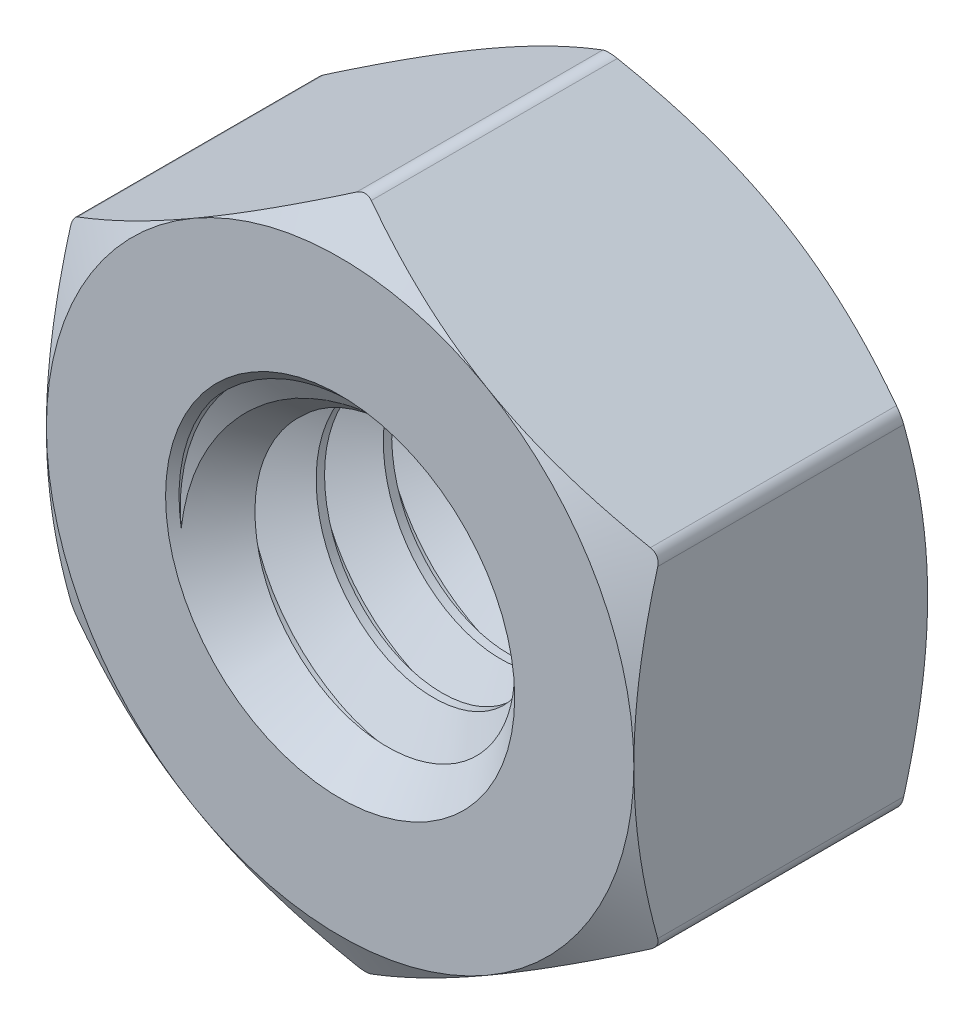
SolidWorks part; units mm, degrees
ref_plane "Front" through (0, 0, 0) normal (0, 0, 1) x (1, 0, 0)
ref_plane "Top" through (0, 0, 0) normal (0, 1, 0) x (1, 0, 0)
ref_plane "Right" through (0, 0, 0) normal (1, 0, 0) x (0, 0, -1)
sketch "Sketch1" plane through (0, 0, 0) normal (0, 0, 1) x (1, 0, 0)
  line L0 (0, 3.175) -> (0, 1.905) construction
  line L1 (-5.5563, 3.2079) -> (-5.5562, -3.2079)
  line L2 (-5.5562, -3.2079) -> (0, -6.4158)
  line L3 (0, -6.4158) -> (5.5562, -3.2079)
  line L4 (5.5562, -3.2079) -> (5.5562, 3.2079)
  line L5 (5.5562, 3.2079) -> (0, 6.4158)
  line L6 (0, 6.4158) -> (-5.5563, 3.2079)
  circle A0 centre (0, 0) radius 5.5562 construction
  circle A1 centre (0, 0) radius 3.175 construction
  point P10 (0, 3.175)
  dimension "Width" = 11.1125
  dimension "Thread Size" = 6.35
  dimension "Thread Pitch" = 1.27
sketch "Sketch2" plane through (0, 0, 0) normal (1, 0, 0) x (0, 0, -1)
  line L0 (-2.7781, 0) -> (2.7781, 0) construction
  line L1 (-2.7781, 6.4158) -> (2.7781, 6.4158) construction
  dimension "Height" = 5.5562
sketch "Sketch15" plane through (0, 0, 0) normal (0, 0, 1) x (1, 0, 0)
  line L1 (0, 6.4158) -> (-5.5563, 3.2079)
  line L2 (-5.5563, 3.2079) -> (-5.5563, -3.2079)
  line L3 (-5.5563, -3.2079) -> (0, -6.4158)
  line L4 (0, -6.4158) -> (5.5563, -3.2079)
  line L5 (5.5563, -3.2079) -> (5.5563, 3.2079)
  line L6 (5.5563, 3.2079) -> (0, 6.4158)
  circle A0 centre (0, 0) radius 5.5563 construction
extrude "Boss-Extrude2" add sketch "Sketch15" along normal mid plane 5.5562
sketch "Sketch16" plane through (0, 0, 0) normal (0, 0, 1) x (1, 0, 0)
  circle A0 centre (0, 0) radius 3.175 construction
  circle A1 centre (0, 0) radius 3.175
sketch "Sketch4" plane through (0, 0, -2.7781) normal (0, 0, -1) x (-1, 0, 0)
  circle A0 centre (0, 0) radius 3.175 construction
  circle A1 centre (0, 0) radius 3.175
extrude "Cut-Extrude4" cut sketch "Sketch16" against normal through all both and the other way through all
sketch "Sketch7" plane through (0, 0, 2.7781) normal (0, 0, 1) x (1, 0, 0)
  circle A0 centre (0, 0) radius 5.5562 construction
  circle A1 centre (0, 0) radius 5.5562
extrude "Cut-Extrude5" cut sketch "Sketch7" against normal through all draft 60 flip side to cut
mirror "Mirror4" about plane through (0, 0, 0) normal (0, 0, 1) of "Cut-Extrude5"
fillet "Fillet2" radius 0.2778 6 edges at (-5.5563, 3.2079, 0) (-5.5563, -3.2079, 0) (0, -6.4158, 0) (5.5563, -3.2079, 0) (5.5563, 3.2079, 0) (0, 6.4158, 0)
sketch "Sketch8" plane through (0, 0, 2.7781) normal (0, 0, 1) x (1, 0, 0)
  line L0 (0.8218, -3.0668) -> (0, 0) construction
  line L2 (0, 3.175) -> (0, 1.905) construction
  circle A0 centre (0, 0) radius 3.175 construction
  point P0 (0.8218, -3.0668)
  dimension "D1" = 15
sketch "Sketch13" plane through (0, 0, -2.7781) normal (0, 0, -1) x (-1, 0, 0)
  circle A0 centre (0, 0) radius 3.175 construction
  circle A1 centre (0, 0) radius 3.175
extrude "Boss-Extrude1" add sketch "Sketch13" against normal up to surface (5.5563 mm away) separate body up to face at (3.175, 0, 2.7781)
curve "Helix/Spiral3" pitch 1.27 height 6.8262 radius 3.175 centre (0, 0, -2.7781) axis (0, 0, 1) start towards (0, 1, 0)
sketch "Sketch12" plane through (0, 0, 0) normal (1, 0, 0) x (0, 0, -1)
  line L0 (3.8894, 3.175) -> (2.7781, 3.175)
  line L1 (3.8894, 3.175) -> (3.4131, 2.3501)
  line L2 (3.4131, 2.3501) -> (3.2544, 2.3501)
  line L3 (3.2544, 2.3501) -> (2.7781, 3.175)
  line L4 (3.3337, 2.3501) -> (3.3337, 3.175) construction
  line L5 (3.0162, 2.7626) -> (3.6512, 2.7626) construction
  dimension "D1" = 60
  dimension "D2" = 0.1588
  dimension "D3" = 0.635
sweep "Cut-Sweep1" cut profiles "Sketch12" path "Helix/Spiral3" align with end faces yes
sketch "Sketch17" plane through (0, 0, 2.7781) normal (0, 0, 1) x (1, 0, 0)
  circle A1 centre (0, 0) radius 3.175
  circle A2 centre (0, 0) radius 3.175
  dimension "D1" = 0
extrude "Boss-Extrude3" add sketch "Sketch17" against normal up to surface (5.5563 mm away) up to face at (3.175, 0, -2.7781)
combine bodies "Combine1" operation type subtract main body 127 bodies to subtract 118
sketch "Sketch10" plane through (0, 0, 2.7781) normal (0, 0, 1) x (1, 0, 0)
  circle A0 centre (0, 0) radius 3.175 construction
  circle A1 centre (0, 0) radius 3.175 construction
  circle A2 centre (0, 0) radius 3.302
  dimension "D1" = 0.127
extrude "Cut-Extrude2" cut sketch "Sketch10" against normal through all draft 45
sketch "Sketch11" plane through (0, 0, -2.7781) normal (0, 0, -1) x (-1, 0, 0)
  circle A1 centre (0, 0) radius 3.302 construction
  circle A2 centre (0, 0) radius 3.302
extrude "Cut-Extrude3" cut sketch "Sketch11" against normal through all draft 45
equation "\"D1\"= \"Height@Sketch2\""
equation "\"D3@Helix/Spiral3\"=\"Height@Sketch2\"+\"Thread Pitch@Sketch1\""
equation "\"D4@Helix/Spiral3\"=\"Thread Pitch@Sketch1\""
equation "\"D2@Sketch12\" = \"D4@Helix/Spiral3\"*.125"
equation "\"D3@Sketch12\" = \"D4@Helix/Spiral3\"*.50"
equation "\"D1@Boss-Extrude2\"=\"Height@Sketch2\""
equation "\"D1@Fillet2\"=\"Width@Sketch1\"*0.025"
equation "\"D1@Sketch10\"=\"Thread Pitch@Sketch1\"*0.1"
